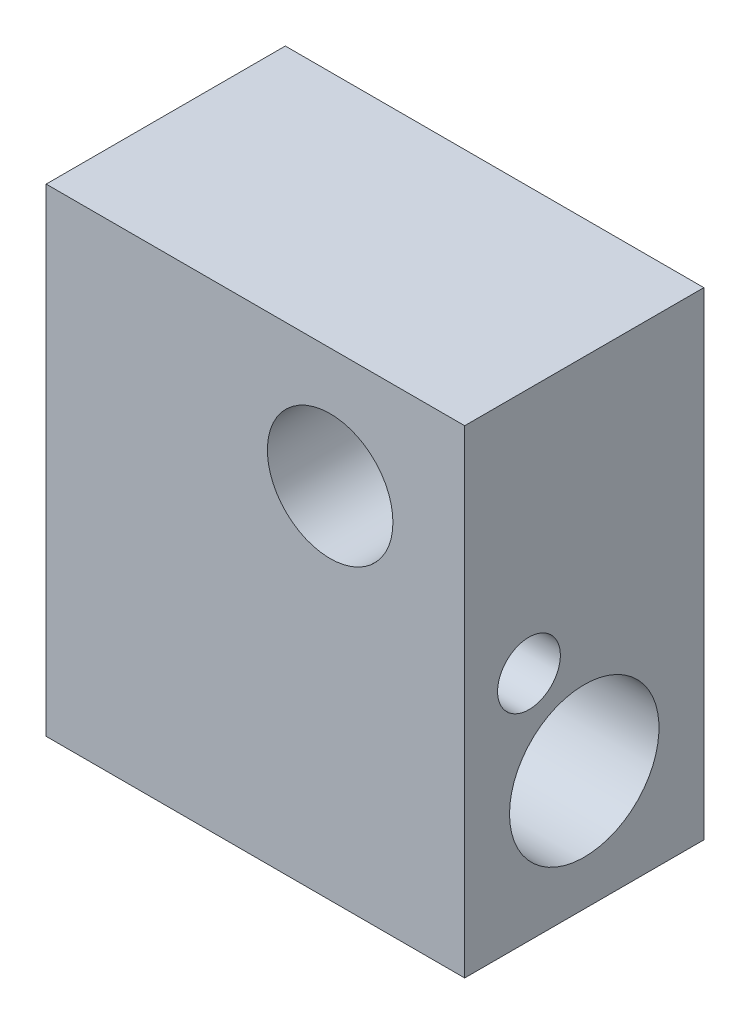
SolidWorks part; units mm, degrees
ref_plane "Front Plane" through (0, 0, 0) normal (0, 0, 1) x (1, 0, 0)
ref_plane "Top Plane" through (0, 0, 0) normal (0, 1, 0) x (1, 0, 0)
ref_plane "Right Plane" through (0, 0, 0) normal (1, 0, 0) x (0, 0, -1)
sketch "Sketch1" plane through (0, 0, 0) normal (0, 0, 1) x (1, 0, 0)
  line L1 (0, 0) -> (14, 0)
  line L2 (0, 0) -> (0, 16)
  line L3 (0, 16) -> (14, 16)
  line L4 (14, 0) -> (14, 16)
  dimension "D1" = 16
  dimension "D2" = 14
extrude "Boss-Extrude1" add sketch "Sketch1" along normal blind 8
hole_wizard "Tap Drill for M5x0.8 Tap1" positions "Sketch3" profile "Sketch2" hole size "M5x0.8" standard "Ansi Metric" end condition through all
sketch "Sketch3" plane through (0, 0, 8) normal (0, 0, 1) x (1, 0, 0)
  line L0 (14, 0) -> (14, 16) construction
  line L1 (14, 16) -> (0, 16) construction
  point P0 (9.5, 12)
  dimension "D1" = 4.5
  dimension "D2" = 4
sketch "Sketch2" plane through (9.5, 12, 8) normal (1, 0, 0) x (0, -1, 0)
  line L0 (0, 0) -> (0, 8)
  line L1 (0, 8) -> (2.1, 8)
  line L2 (2.1, 8) -> (2.1, 0)
  line L5 (2.1, 0) -> (0, 0)
  line L11 (0, -6.35) -> (0, 107.95) construction
  dimension "Thru Hole Dia." = 4.2
  dimension "Thru Hole Depth" = 8
ref_axis "Axis1" through (9.5, 12, 0) along (0, 0, 1)
hole_wizard "Ø5.0 (5) Diameter Hole1" positions "Sketch5" profile "Sketch4" hole size "Ø5.0" standard "Ansi Metric" end condition through all
sketch "Sketch5" plane through (0, 0, 0) normal (-1, 0, 0) x (0, 0, 1)
  line L0 (4, 0) -> (4, 7.9761) construction
  line L1 (8, 0) -> (0, 0) construction
  point P0 (4, 4)
  dimension "D1" = 4
sketch "Sketch4" plane through (0, 4, 4) normal (0, 1, 0) x (0, 0, 1)
  line L0 (0, 0) -> (0, 14)
  line L1 (0, 14) -> (2.5, 14)
  line L2 (2.5, 14) -> (2.5, 0)
  line L5 (2.5, 0) -> (0, 0)
  line L11 (0, -6.35) -> (0, 107.95) construction
  dimension "Thru Hole Dia." = 5
  dimension "Thru Hole Depth" = 14
hole_wizard "Ø2.1 (2.1) Diameter Hole1" positions "Sketch9" profile "Sketch8" hole size "Ø2.1" standard "Ansi Metric" end condition through all
sketch "Sketch9" plane through (0, 0, 0) normal (-1, 0, 0) x (0, 0, 1)
  line L0 (4, 16) -> (4, 0) construction
  line L1 (8, 16) -> (0, 16) construction
  line L3 (8, 0) -> (0, 0) construction
  line L5 (0, 16) -> (0, 0) construction
  point P0 (5.85, 7.75)
  dimension "D1" = 8.25
  dimension "D2" = 5.85
sketch "Sketch8" plane through (0, 7.75, 5.85) normal (0, 1, 0) x (0, 0, 1)
  line L0 (0, 0) -> (0, 14)
  line L1 (0, 14) -> (1.05, 14)
  line L2 (1.05, 14) -> (1.05, 0)
  line L5 (1.05, 0) -> (0, 0)
  line L11 (0, -6.35) -> (0, 107.95) construction
  dimension "Thru Hole Dia." = 2.1
  dimension "Thru Hole Depth" = 14
